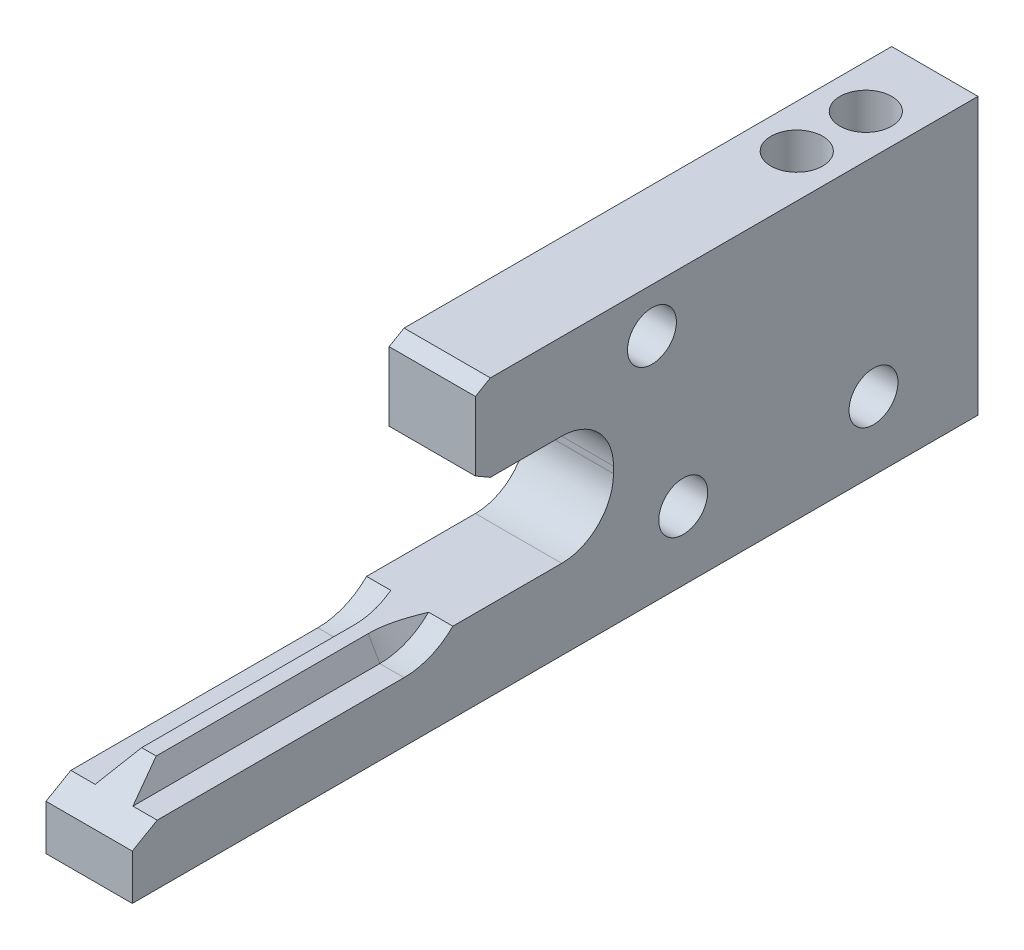
SolidWorks part; units mm, degrees
material "4140/42 H.R STEEL"
ref_plane "Front Plane" through (0, 0, 0) normal (0, 0, 1) x (1, 0, 0)
ref_plane "Top Plane" through (0, 0, 0) normal (0, 1, 0) x (1, 0, 0)
ref_plane "Right Plane" through (0, 0, 0) normal (1, 0, 0) x (0, 0, -1)
sketch "Sketch1" plane through (0, 0, 0) normal (1, 0, 0) x (0, 0, -1)
  line L0 (0, 0) -> (-155.575, 0)
  line L1 (-155.575, 0) -> (-155.575, 14.6939)
  line L2 (-155.575, 14.6939) -> (-76.581, 14.6939)
  line L3 (-67.056, 24.2189) -> (-67.056, 25.4254)
  line L4 (-76.581, 34.9504) -> (-89.7064, 34.9504)
  line L5 (-89.7064, 34.9504) -> (-92.456, 36.5379)
  line L6 (-92.456, 36.5379) -> (-92.456, 49.2125)
  line L7 (-92.456, 49.2125) -> (-89.7064, 50.8)
  line L8 (-89.7064, 50.8) -> (0, 50.8)
  line L9 (0, 50.8) -> (0, 0)
  line L11 (-92.456, 42.8752) -> (-117.475, 42.8752) construction
  arc A0 (-67.056, 25.4254) -> (-76.581, 34.9504) centre (-76.581, 25.4254) ccw
  arc A1 (-76.581, 14.6939) -> (-67.056, 24.2189) centre (-76.581, 24.2189) ccw
  circle A2 centre (-117.475, 42.8752) radius 28.1813 construction
  point P3 (-117.475, 42.8752)
  dimension "D11" = 9.525
  dimension "D12" = 9.525
  dimension "D1" = 30
  dimension "D2" = 30
  dimension "D3" = 1.5875
  dimension "D4" = 1.5875
  dimension "D5" = 15.8496
  dimension "D6" = 25.019
  dimension "D7" = 38.1
  dimension "D8" = 28.1813
  dimension "D9" = 50.8
  dimension "D10" = 117.475
  dimension "D13" = 25.4
extrude "Extrude1" add sketch "Sketch1" along normal blind 15.875
sketch "Sketch2" plane through (0, 0, 155.575) normal (0, 0, 1) x (1, 0, 0)
  line L0 (0, 10.9855) -> (4.463, 10.9855)
  line L1 (0, 14.6939) -> (0, 0) construction
  line L2 (4.463, 10.9855) -> (6.604, 14.6939)
  line L3 (15.875, 14.6939) -> (0, 14.6939) construction
  line L4 (6.604, 14.6939) -> (9.271, 14.6939)
  line L5 (9.271, 14.6939) -> (11.412, 10.9855)
  line L6 (11.412, 10.9855) -> (15.875, 10.9855)
  line L7 (15.875, 14.6939) -> (15.875, 0) construction
  line L8 (15.875, 10.9855) -> (15.875, 23.6855)
  line L9 (15.875, 23.6855) -> (0, 23.6855)
  line L10 (0, 23.6855) -> (0, 10.9855)
  line L11 (7.9375, 14.6939) -> (7.9375, 23.6855) construction
  dimension "D1" = 2.667
  dimension "D2" = 60
  dimension "D3" = 30
  dimension "D4" = 3.7084
  dimension "D5" = 12.7
extrude "Extrude2" cut sketch "Sketch2" against normal blind 50
sketch "Sketch3" plane through (0, 0, 105.575) normal (0, 0, 1) x (1, 0, 0)
  line L8 (0, 10.9855) -> (4.463, 10.9855)
  line L9 (4.463, 10.9855) -> (6.604, 14.6939)
  line L10 (6.604, 14.6939) -> (9.271, 14.6939)
  line L11 (9.271, 14.6939) -> (11.412, 10.9855)
  line L12 (11.412, 10.9855) -> (15.875, 10.9855)
  line L13 (15.875, 10.9855) -> (15.875, 23.6855)
  line L14 (15.875, 23.6855) -> (0, 23.6855)
  line L15 (0, 23.6855) -> (0, 10.9855)
  line L16 (0, 10.9855) -> (4.463, 10.9855)
  line L17 (4.463, 10.9855) -> (6.604, 14.6939)
  line L18 (6.604, 14.6939) -> (9.271, 14.6939)
  line L19 (9.271, 14.6939) -> (11.412, 10.9855)
  line L20 (11.412, 10.9855) -> (15.875, 10.9855)
  line L21 (15.875, 10.9855) -> (15.875, 23.6855)
  line L22 (15.875, 23.6855) -> (0, 23.6855)
  line L23 (0, 23.6855) -> (0, 10.9855)
  dimension "D1" = 0
revolve "Cut-Revolve1" cut sketch "Sketch3" angle 360 about L22
ref_axis "Axis1" through (0, 42.8752, 117.475) along (1, 0, 0)
hole_wizard "3/8 (0.375) Diameter Hole1" positions "Sketch5" profile "Sketch4" hole size "3/8" standard "Ansi Inch"
sketch "Sketch5" plane through (0, 50.8, 0) normal (0, 1, 0) x (-1, 0, 0)
  line L0 (0, 117.475) -> (-54.0074, 117.475) construction
  line L1 (-7.9375, 25.4) -> (-7.9375, 0) construction
  line L2 (-15.875, 0) -> (0, 0) construction
  point P0 (-7.9375, 25.4)
  point P1 (-7.9375, 12.7)
  dimension "D1" = 12.7
  dimension "D2" = 92.075
sketch "Sketch4" plane through (7.9375, 50.8, 25.4) normal (1, 0, 0) x (0, 0, 1)
  line L0 (0, 0) -> (0, 34.1334)
  line L1 (0, 34.1334) -> (4.7625, 32.4)
  line L2 (4.7625, 32.4) -> (4.7625, 0)
  line L5 (4.7625, 0) -> (0, 0)
  line L10 (0, 34.1334) -> (-4.7625, 32.4) construction
  line L11 (0, -6.35) -> (0, 107.95) construction
  dimension "Hole Dia." = 9.525
  dimension "Hole Depth" = 32.4
  dimension "Drill Angle" = 140
sketch "Sketch6" plane through (15.875, 0, 0) normal (1, 0, 0) x (0, 0, -1)
  line L0 (0, 50.8) -> (-89.7064, 50.8) construction
  line L1 (0, 0) -> (0, 50.8) construction
  line L2 (-155.575, 8.3439) -> (-144.5765, 14.6939)
  line L3 (-155.575, 10.9855) -> (-155.575, 0) construction
  line L4 (-76.581, 14.6939) -> (-96.6061, 14.6939) construction
  line L5 (-144.5765, 14.6939) -> (-155.575, 14.6939)
  line L6 (-155.575, 14.6939) -> (-155.575, 8.3439)
  circle A0 centre (-54.23, 12.61) radius 4.5
  circle A1 centre (-19.23, 12.61) radius 4.5
  circle A2 centre (-59.98, 42.61) radius 4.5
  dimension "D1" = 9
  dimension "D2" = 35
  dimension "D3" = 38.19
  dimension "D4" = 19.23
  dimension "D5" = 30
  dimension "D6" = 5.75
  dimension "D7" = 6.35
  dimension "D8" = 30
extrude "Extrude3" cut sketch "Sketch6" against normal through all
ref_plane "Plane1" through (7.9375, 0, 0) normal (1, 0, 0) x (0, 0, -1)
ref_plane "Plane2" through (19.1135, 0, 0) normal (1, 0, 0) x (0, 0, -1)
ref_plane "Plane3" through (-3.2385, 0, 0) normal (1, 0, 0) x (0, 0, -1)
other "Freeze***"
